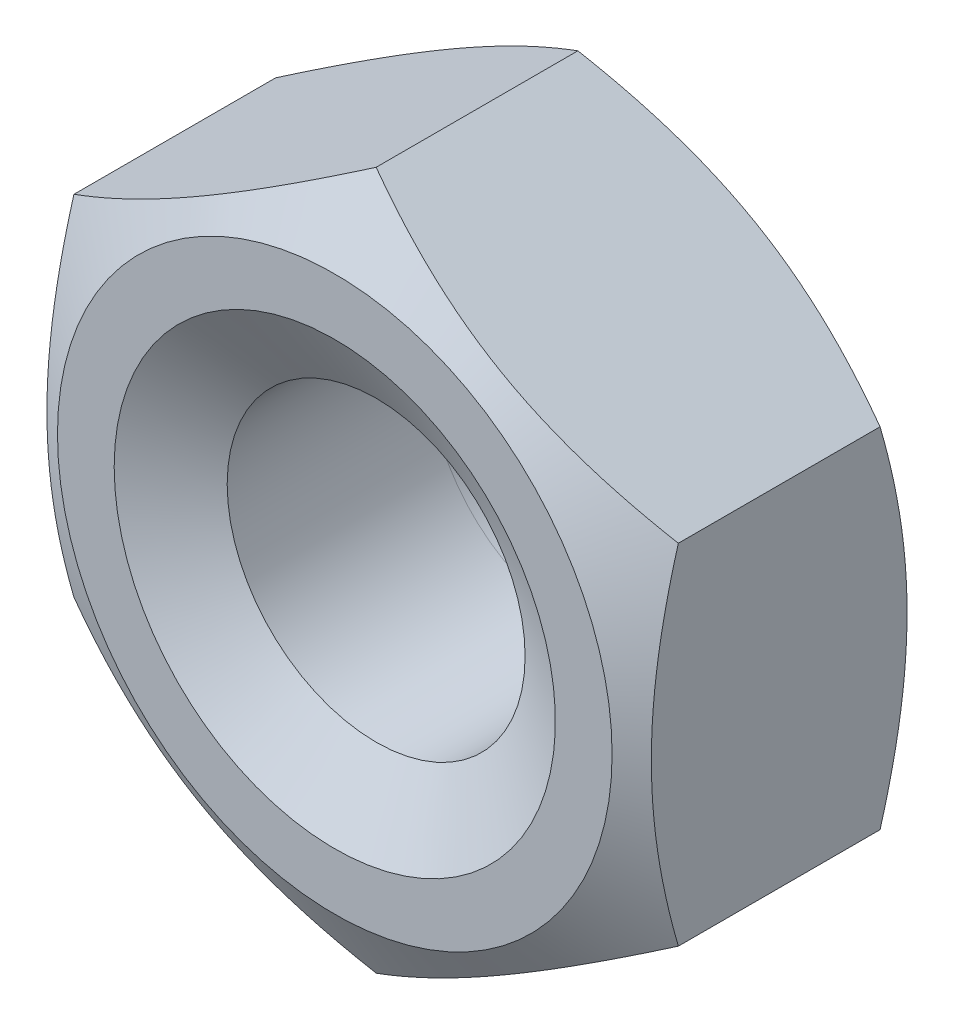
SolidWorks part; units mm, degrees
other "Ссылка на сопряжения"
material "AISI 316 Нержавеющая сталь, лист (SS)"
ref_plane "Плоскость1" through (0, 0, 0) normal (0, 0, 1) x (1, 0, 0)
ref_plane "Плоскость2" through (0, 0, 0) normal (0, 1, 0) x (1, 0, 0)
ref_plane "Плоскость3" through (0, 0, 0) normal (1, 0, 0) x (0, 0, -1)
sketch "Эскиз1" plane through (0, 0, 0) normal (0, 0, 1) x (1, 0, 0)
  line L1 (0, 9.815) -> (-8.5, 4.9075)
  line L2 (-8.5, 4.9075) -> (-8.5, -4.9075)
  line L3 (-8.5, -4.9075) -> (0, -9.815)
  line L4 (0, -9.815) -> (8.5, -4.9075)
  line L5 (8.5, -4.9075) -> (8.5, 4.9075)
  line L6 (8.5, 4.9075) -> (0, 9.815)
  circle A0 centre (0, 0) radius 8.5 construction
  circle A1 centre (0, 0) radius 4.19
  dimension "rezba" = 8.38
  dimension "S" = 17
extrude "Основание-Вытянуть" add sketch "Эскиз1" along normal blind 8
cosmetic thread "Условное изображение резьбы1" parameters "d"=10
sketch "Эскиз2" plane through (0, 0, 0) normal (1, 0, 0) x (0, 0, -1)
  line L0 (-8, 4.9075) -> (-8, 9.815) construction
  line L1 (-8, 9.815) -> (0, 9.815) construction
  line L2 (-8, 7.8) -> (-8, 9.815)
  line L3 (-8, 9.815) -> (-6.8367, 9.815)
  line L4 (-8, 7.8) -> (-6.8367, 9.815)
  line L5 (0, 0) -> (-8, 0) construction
  line L6 (-8, 0) -> (0, 0) construction
  line L7 (-8, -4.9075) -> (-8, 4.9075) construction
  line L8 (0, 4.19) -> (-8, 4.19) construction
  line L9 (-6.8367, 4.19) -> (-8, 4.19)
  line L10 (-8, 6.205) -> (-6.8367, 4.19)
  line L11 (-8, 6.205) -> (-8, 4.19)
  line L12 (-4, 0) -> (-4, 3.9594) construction
  line L13 (0, 6.205) -> (0, 4.19)
  line L14 (0, 6.205) -> (-1.1633, 4.19)
  line L15 (-1.1633, 4.19) -> (0, 4.19)
  line L16 (0, 7.8) -> (-1.1633, 9.815)
  line L17 (0, 9.815) -> (-1.1633, 9.815)
  line L18 (0, 7.8) -> (0, 9.815)
  dimension "D1" = 15.6
  dimension "_" = 30
revolve "Вырез-Повернуть1" cut sketch "Эскиз2" angle 360 about L5
revolve "Скрытый" add sketch "Эскиз2<3>" angle 360 about L5 region at (0, 4.8617, 0.3878)
sketch "Эскиз2<3>" plane through (0, 0, 0) normal (1, 0, 0) x (0, 0, -1) same geometry as "Эскиз2"
